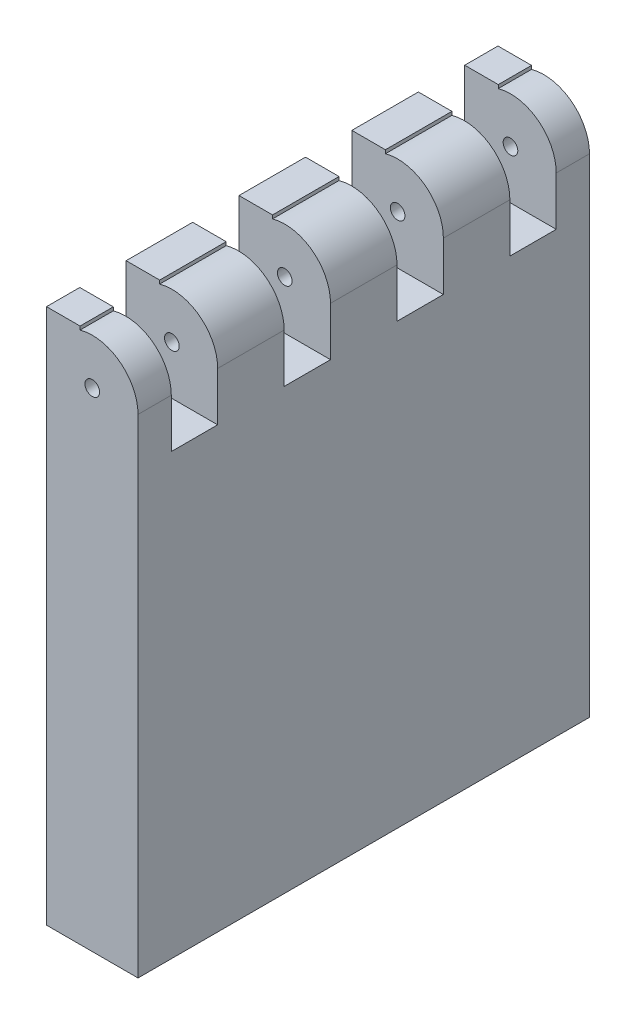
SolidWorks part; units mm, degrees
ref_plane "Front Plane" through (0, 0, 0) normal (0, 0, 1) x (1, 0, 0)
ref_plane "Top Plane" through (0, 0, 0) normal (0, 1, 0) x (1, 0, 0)
ref_plane "Right Plane" through (0, 0, 0) normal (1, 0, 0) x (0, 0, -1)
sketch "Sketch1" plane through (0, 0, 0) normal (0, 0, 1) x (1, 0, 0)
  line L2 (7.5, 0) -> (7.5, -80)
  line L3 (7.5, -80) -> (-7.5, -80)
  line L4 (-7.5, 0) -> (-7.5, -80)
  arc A0 (7.5, 0) -> (-7.5, 0) centre (0, 0) ccw
  dimension "D4" = 15
  dimension "D1" = 15
  dimension "D2" = 7.5
  dimension "D3" = 80
extrude "Boss-Extrude1" add sketch "Sketch1" along normal mid plane 74
sketch "Sketch2" plane through (0, 0, 0) normal (0, 0, 1) x (1, 0, 0)
  line L1 (-7.5, 0) -> (-2, 0)
  line L2 (-7.5, 0) -> (-7.5, 7.8)
  line L3 (-7.5, 7.8) -> (-2, 7.8)
  line L4 (-2, 0) -> (-2, 7.8)
  dimension "D1" = 2
  dimension "D2" = 7.8
extrude "Boss-Extrude2" add sketch "Sketch2" along normal mid plane 74
sketch "Sketch3" plane through (0, 0, 0) normal (1, 0, 0) x (0, 0, -1)
  line L0 (0, 8.25) -> (0, -8.25) construction
  line L1 (-5.45, -8) -> (-13.05, -8)
  line L2 (-5.45, -8) -> (-5.45, 9)
  line L3 (-5.45, 9) -> (-13.05, 9)
  line L4 (-13.05, -8) -> (-13.05, 9)
  line L5 (-23.95, -8) -> (-31.55, -8)
  line L6 (-23.95, -8) -> (-23.95, 9)
  line L7 (-23.95, 9) -> (-31.55, 9)
  line L8 (-31.55, -8) -> (-31.55, 9)
  line L9 (31.55, -8) -> (31.55, 9)
  line L10 (23.95, 9) -> (31.55, 9)
  line L11 (23.95, -8) -> (23.95, 9)
  line L12 (23.95, -8) -> (31.55, -8)
  line L13 (13.05, -8) -> (13.05, 9)
  line L14 (5.45, 9) -> (13.05, 9)
  line L15 (5.45, -8) -> (5.45, 9)
  line L16 (5.45, -8) -> (13.05, -8)
  dimension "D1" = 5.45
  dimension "D2" = 13.05
  dimension "D3" = 8
  dimension "D4" = 9
  dimension "D5" = 23.95
  dimension "D6" = 31.55
  dimension "D7" = 9
  dimension "D8" = 8
extrude "Cut-Extrude1" cut sketch "Sketch3" against normal through all both and the other way through all
sketch "Sketch4" plane through (0, 0, 0) normal (0, 0, 1) x (1, 0, 0)
  circle A0 centre (0, 0) radius 1.2
  dimension "D1" = 2.4
extrude "Cut-Extrude2" cut sketch "Sketch4" against normal through all both and the other way through all
